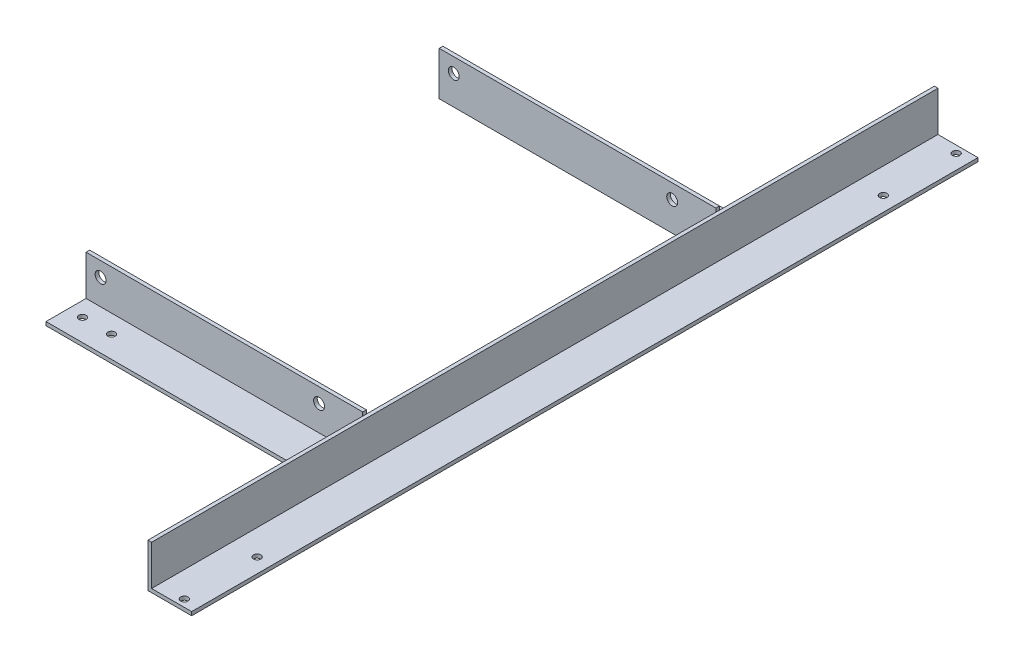
SolidWorks part; units mm, degrees
material "Plain Carbon Steel"
ref_plane "Front Plane" through (0, 0, 0) normal (0, 0, 1) x (1, 0, 0)
ref_plane "Top Plane" through (0, 0, 0) normal (0, 1, 0) x (1, 0, 0)
ref_plane "Right Plane" through (0, 0, 0) normal (1, 0, 0) x (0, 0, -1)
sketch "Sketch1" plane through (0, 0, 0) normal (0, 0, 1) x (1, 0, 0)
  line L0 (0, 0) -> (0, 38.1)
  line L1 (0, -55) -> (0, 55) construction
  line L3 (55, 0) -> (-55, 0) construction
  line L4 (38.1, 0) -> (0, 0)
  dimension "D1" = 38.1
  dimension "D2" = 38.1
extrude "Extrude-Thin1" add sketch "Sketch1" along normal mid plane 685.8 thin thin type one direction wall 3.175
sketch "Sketch2" plane through (0, 0, 0) normal (-1, 0, 0) x (0, 0, 1)
  line L0 (-190.5, 3.175) -> (-152.4, 3.175)
  line L2 (-152.4, 3.175) -> (-152.4, 41.275)
  line L4 (152.4, 3.175) -> (152.4, 41.275)
  line L5 (152.4, 3.175) -> (190.5, 3.175)
  line L6 (153.67, 0) -> (-153.67, 0) construction
  dimension "D1" = 152.4
  dimension "D2" = 152.4
  dimension "D3" = 3.175
  dimension "D4" = 38.1
extrude "Extrude-Thin2" add sketch "Sketch2" along normal blind 241.3 thin thin type one direction reverse wall 3.175
sketch "Sketch3" plane through (0, 3.175, 0) normal (0, -1, 0) x (1, 0, 0)
  line L0 (-241.3, 152.4) -> (-241.3, 190.5) construction
  line L1 (-241.3, 152.4) -> (0, 152.4) construction
  line L2 (-241.3, -152.4) -> (0, -152.4) construction
  circle A0 centre (-228.6, 171.45) radius 3.175
  circle A1 centre (-203.2, 171.45) radius 3.175
  circle A2 centre (-228.6, -171.45) radius 3.175
  circle A3 centre (-203.2, -171.45) radius 3.175
  point P12 (0, 0)
  point P17 (0, 0)
  point P18 (0, 0)
  point P19 (0, 0)
  dimension "D1" = 25.4
  dimension "D4" = 6.35
  dimension "D2" = 12.7
  dimension "D3" = 19.05
  dimension "D5" = 19.05
extrude "Cut-Extrude1" cut sketch "Sketch3" against normal up to next
sketch "Sketch4" plane through (0, 0, 0) normal (0, -1, 0) x (1, 0, 0)
  line L0 (38.1, 342.9) -> (38.1, -342.9) construction
  line L1 (38.1, 342.9) -> (0, 342.9) construction
  line L2 (38.1, -342.9) -> (0, -342.9) construction
  circle A0 centre (25.4, -336.55) radius 3.175
  circle A1 centre (25.4, -273.05) radius 3.175
  circle A2 centre (25.4, 273.05) radius 3.175
  circle A3 centre (25.4, 336.55) radius 3.175
  point P12 (0, 0)
  dimension "D1" = 12.7
  dimension "D6" = 6.35
  dimension "D2" = 6.35
  dimension "D3" = 63.5
  dimension "D4" = 63.5
  dimension "D5" = 6.35
extrude "Cut-Extrude2" cut sketch "Sketch4" against normal up to next
sketch "Sketch5" plane through (0, 0, 0) normal (0, 0, 1) x (1, 0, 0)
  line L0 (-241.3, 41.275) -> (-241.3, 6.35) construction
  line L1 (-241.3, 41.275) -> (0, 41.275) construction
  circle A0 centre (-228.6, 28.575) radius 4.7625
  circle A1 centre (-38.1, 28.575) radius 4.7625
  dimension "D1" = 9.525
  dimension "D2" = 12.7
  dimension "D3" = 12.7
  dimension "D4" = 190.5
extrude "Cut-Extrude3" cut sketch "Sketch5" against normal through all both and the other way through all
